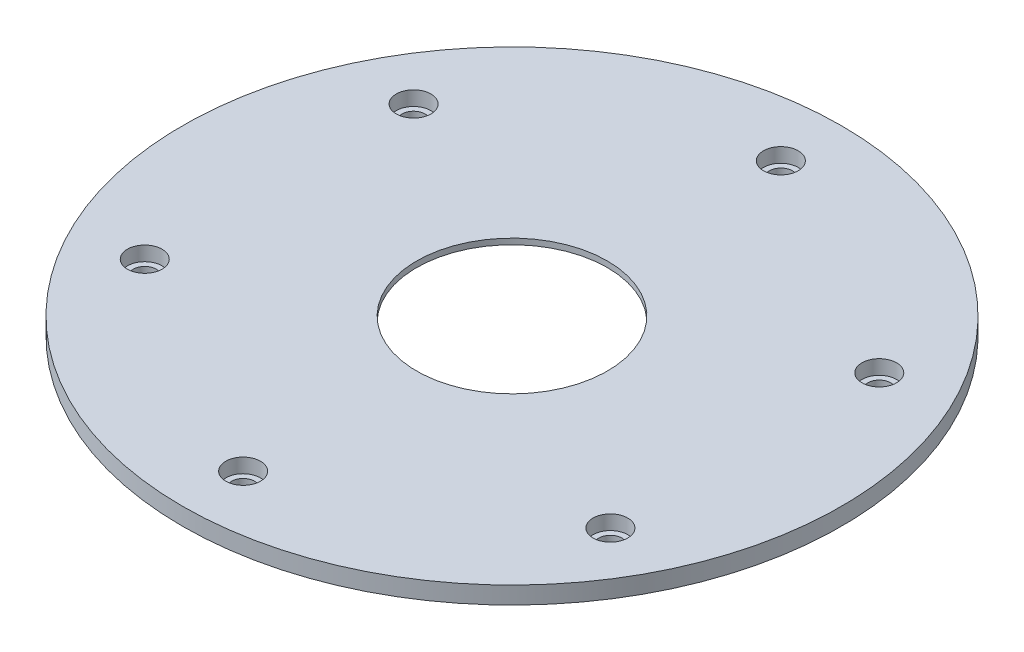
SolidWorks part; units mm, degrees
ref_plane "Front Plane" through (0, 0, 0) normal (0, 0, 1) x (1, 0, 0)
ref_plane "Top Plane" through (0, 0, 0) normal (0, 1, 0) x (1, 0, 0)
ref_plane "Right Plane" through (0, 0, 0) normal (1, 0, 0) x (0, 0, -1)
sketch "Sketch1" plane through (0, 0, 0) normal (0, 1, 0) x (1, 0, 0)
  circle A0 centre (0, 0) radius 57
  dimension "D1" = 114
extrude "Boss-Extrude1" add sketch "Sketch1" along normal blind 3
sketch "Sketch2" plane through (0, 3, 0) normal (0, 1, 0) x (1, 0, 0)
  line L0 (0, 62.5097) -> (0, -64.2706) construction
  circle A0 centre (0, 46.5) radius 2
  dimension "D1" = 4
  dimension "D2" = 46.5
extrude "Cut-Extrude1" cut sketch "Sketch2" against normal through all
pattern_circular "CirPattern1" count 6 over 360 about axis through (0, 3, 0) along (0, 1, 0) of "Cut-Extrude1"
sketch "Sketch5" plane through (0, 0, 0) normal (0, -1, 0) x (1, 0, 0)
  circle A0 centre (0, 46.5) radius 3.25
  circle A1 centre (40.2702, 23.25) radius 3.25
  circle A2 centre (40.2702, -23.25) radius 3.25
  circle A3 centre (0, -46.5) radius 3.25
  circle A4 centre (-40.2702, -23.25) radius 3.25
  circle A5 centre (-40.2702, 23.25) radius 3.25
  dimension "D1" = 6.5
  dimension "D2" = 6.5
extrude "Boss-Extrude2" add sketch "Sketch5" along normal blind 5
sketch "Sketch4" plane through (0, 0, 0) normal (0, -1, 0) x (1, 0, 0)
  circle A0 centre (0, 0) radius 16.5
  dimension "D1" = 33
extrude "Cut-Extrude3" cut sketch "Sketch4" against normal through all
sketch "Sketch8" plane through (0, 3, 0) normal (0, 1, 0) x (1, 0, 0)
  circle A0 centre (-40.2702, -23.25) radius 2 construction
  circle A1 centre (0, -46.5) radius 2 construction
  circle A2 centre (40.2702, -23.25) radius 2 construction
  circle A3 centre (40.2702, 23.25) radius 2 construction
  circle A4 centre (0, 46.5) radius 2 construction
  circle A5 centre (-40.2702, 23.25) radius 2 construction
  circle A6 centre (-40.2702, -23.25) radius 2
  circle A7 centre (0, -46.5) radius 2
  circle A8 centre (40.2702, -23.25) radius 2
  circle A9 centre (40.2702, 23.25) radius 2
  circle A10 centre (0, 46.5) radius 2
  circle A11 centre (-40.2702, 23.25) radius 2
extrude "Cut-Extrude4" cut sketch "Sketch8" against normal through all
sketch "Sketch9" plane through (0, 3, 0) normal (0, 1, 0) x (1, 0, 0)
  circle A0 centre (-40.2702, 23.25) radius 3
  circle A1 centre (0, 46.5) radius 3
  circle A2 centre (40.2702, 23.25) radius 3
  circle A3 centre (40.2702, -23.25) radius 3
  circle A4 centre (0, -46.5) radius 3
  circle A5 centre (-40.2702, -23.25) radius 3
  dimension "D1" = 6
extrude "Cut-Extrude5" cut sketch "Sketch9" against normal blind 2.5
sketch "Sketch11" plane through (0, 0, 0) normal (0, -1, 0) x (1, 0, 0)
  line L0 (0, 0) -> (0, 60.7001) construction
  line L1 (0, 0) -> (62.0393, 35.8184) construction
  arc A2 (-50.0231, 17.5126) -> (-50.0231, -17.5126) centre (0, 0) ccw
  circle A3 centre (0, 0) radius 57 construction
  arc A5 (5.1661, 47.4349) -> (9.8452, 52.0776) centre (9.1022, 48.1472) cw
  circle A6 centre (0, 46.5) radius 5.25
  arc A7 (-5.1661, 47.4349) -> (5.1661, 47.4349) centre (0, 46.5) ccw
  arc A8 (-5.1661, 47.4349) -> (-9.8452, 52.0776) centre (-9.1022, 48.1472) ccw
  arc A9 (38.4968, 28.1914) -> (40.1779, 34.565) centre (37.1456, 31.9563) ccw
  arc A10 (38.4968, 28.1914) -> (43.6629, 19.2435) centre (40.2702, 23.25) ccw
  arc A11 (43.6629, 19.2435) -> (50.0231, 17.5126) centre (46.2478, 16.1909) cw
  arc A12 (43.6629, -19.2435) -> (50.0231, -17.5126) centre (46.2478, -16.1909) ccw
  arc A13 (43.6629, -19.2435) -> (38.4968, -28.1914) centre (40.2702, -23.25) ccw
  arc A14 (38.4968, -28.1914) -> (40.1779, -34.565) centre (37.1456, -31.9563) cw
  arc A15 (5.1661, -47.4349) -> (9.8452, -52.0776) centre (9.1022, -48.1472) ccw
  arc A16 (5.1661, -47.4349) -> (-5.1661, -47.4349) centre (0, -46.5) ccw
  arc A17 (-5.1661, -47.4349) -> (-9.8452, -52.0776) centre (-9.1022, -48.1472) cw
  arc A18 (-38.4968, -28.1914) -> (-40.1779, -34.565) centre (-37.1456, -31.9563) ccw
  arc A19 (-38.4968, -28.1914) -> (-43.6629, -19.2435) centre (-40.2702, -23.25) ccw
  arc A20 (-43.6629, -19.2435) -> (-50.0231, -17.5126) centre (-46.2478, -16.1909) cw
  arc A21 (-43.6629, 19.2435) -> (-50.0231, 17.5126) centre (-46.2478, 16.1909) ccw
  arc A22 (-43.6629, 19.2435) -> (-38.4968, 28.1914) centre (-40.2702, 23.25) ccw
  arc A23 (-38.4968, 28.1914) -> (-40.1779, 34.565) centre (-37.1456, 31.9563) cw
  arc A24 (-9.8452, 52.0776) -> (-40.1779, 34.565) centre (0, 0) ccw
  arc A25 (40.1779, 34.565) -> (9.8452, 52.0776) centre (0, 0) ccw
  arc A26 (50.0231, -17.5126) -> (50.0231, 17.5126) centre (0, 0) ccw
  arc A27 (9.8452, -52.0776) -> (40.1779, -34.565) centre (0, 0) ccw
  arc A28 (-40.1779, -34.565) -> (-9.8452, -52.0776) centre (0, 0) ccw
  point P52 (0, 0)
  dimension "D2" = 4
  dimension "D3" = 2
  dimension "D4" = 4
  dimension "D5" = 4
  dimension "D1" = 60
  dimension "D6" = 6
extrude "Cut-Extrude7" cut sketch "Sketch11" against normal blind 2
pattern_circular "CirPattern3" count 6 over 360 of "Cut-Extrude7"
sketch "Sketch12" plane through (0, 2, 0) normal (0, -1, 0) x (1, 0, 0)
  circle A0 centre (0, 0) radius 25
  circle A1 centre (0, 0) radius 22.5
  dimension "D1" = 50
  dimension "D2" = 45
extrude "Boss-Extrude3" add sketch "Sketch12" along normal blind 2
